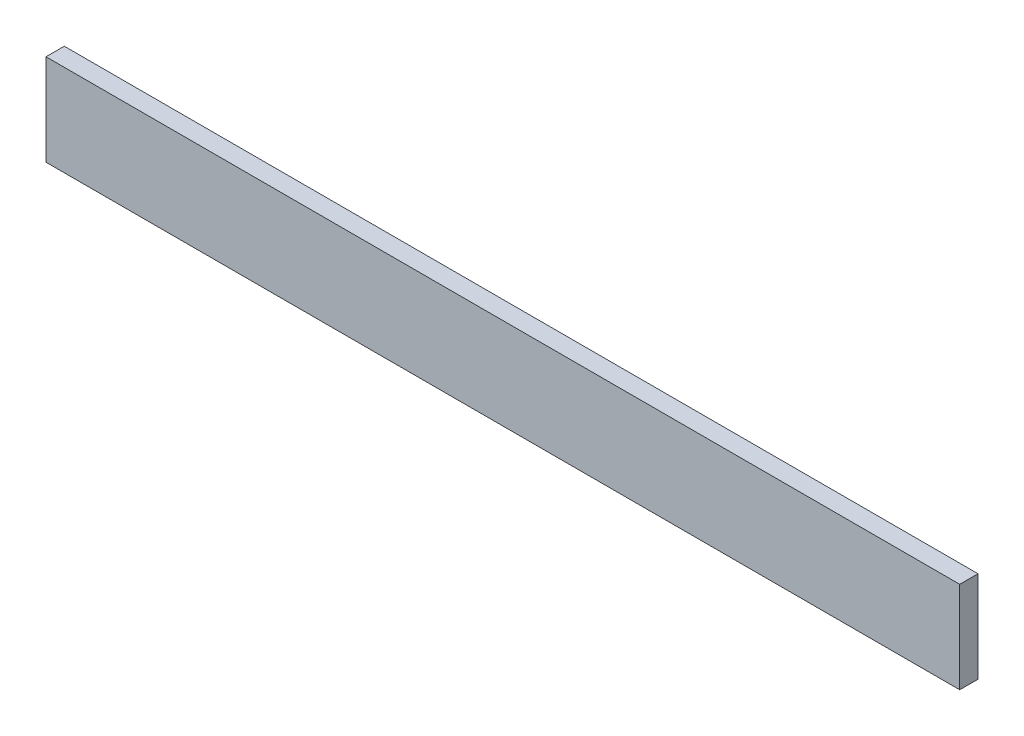
SolidWorks part; units mm, degrees
ref_plane "Front Plane" through (0, 0, 0) normal (0, 0, 1) x (1, 0, 0)
ref_plane "Top Plane" through (0, 0, 0) normal (0, 1, 0) x (1, 0, 0)
ref_plane "Right Plane" through (0, 0, 0) normal (1, 0, 0) x (0, 0, -1)
sketch "Sketch1" plane through (0, 0, 0) normal (0, 0, 1) x (1, 0, 0)
  line L0 (0, 0) -> (300, 0)
  line L1 (300, 0) -> (300, 30)
  line L2 (300, 30) -> (0, 30)
  line L3 (0, 30) -> (0, 0)
extrude "Boss-Extrude1" add sketch "Sketch1" along normal blind 6
